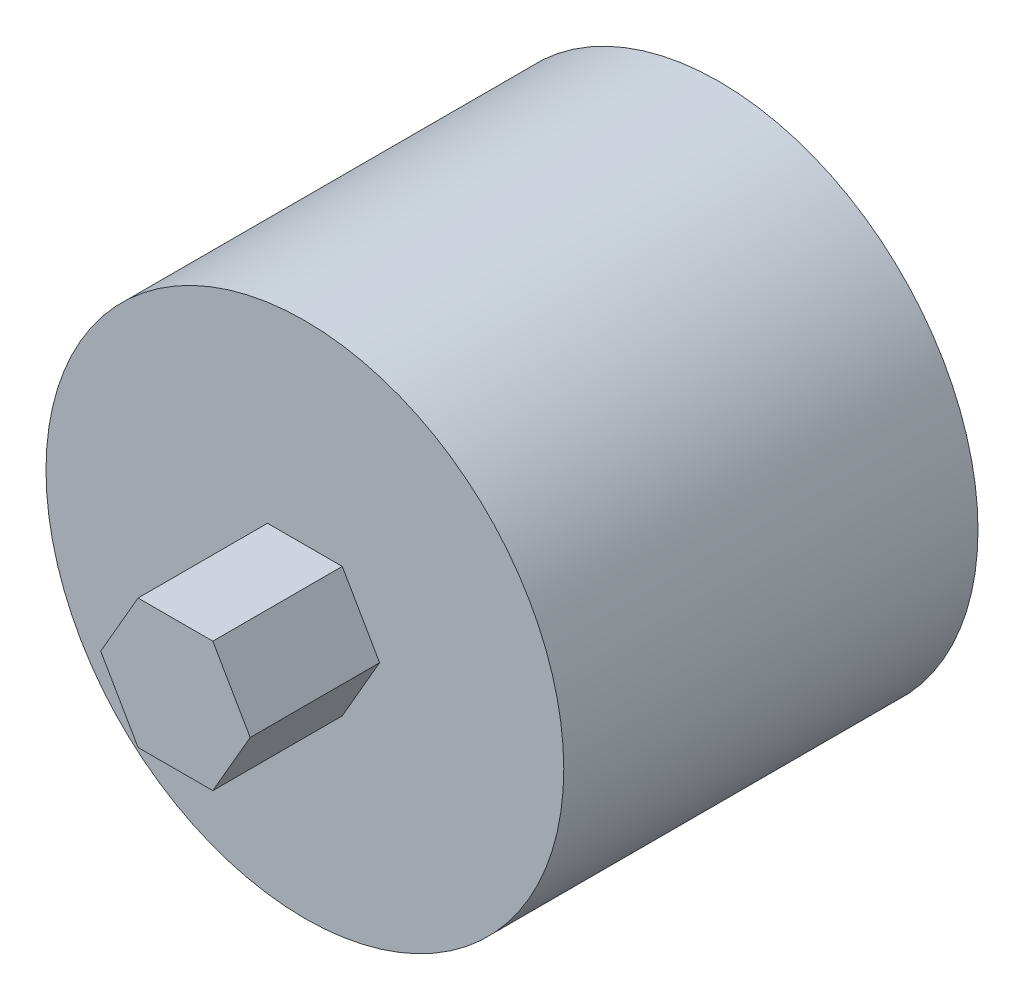
SolidWorks part; units mm, degrees
ref_plane "前视基准面" through (0, 0, 0) normal (0, 0, 1) x (1, 0, 0)
ref_plane "上视基准面" through (0, 0, 0) normal (0, 1, 0) x (1, 0, 0)
ref_plane "右视基准面" through (0, 0, 0) normal (1, 0, 0) x (0, 0, -1)
other "Configuration Table"
sketch "草图1" plane through (0, 0, 0) normal (0, 0, 1) x (1, 0, 0)
  line L0 (0, 0) -> (1.6914, 0.6156) construction
  line L1 (0, 0) -> (1.5832, 0.5954)
  line L2 (0, 0) -> (1.5832, -0.5954)
  line L3 (0, 0) -> (1.6914, -0.6156) construction
  line L4 (0, 0) -> (2.55, 0) construction
  line L5 (1.6914, 0.6156) -> (1.6914, -0.6156) construction
  circle A0 centre (0, 0) radius 1.65
  circle A1 centre (0, 0) radius 2.55
  circle A2 centre (0, 0) radius 1.6914 construction
  circle A3 centre (0, 0) radius 1.8 construction
  circle A4 centre (0, 0) radius 3
  spline S0 degree 4 poles (1.5832, 0.5954) (1.5953, 0.5999) (1.6299, 0.61) (1.6985, 0.6188) (1.8107, 0.6176) (1.9542, 0.5935) (2.1323, 0.5368) (2.3288, 0.4397) (2.527, 0.3033) (2.7182, 0.1281) (2.8863, -0.0692) (3.0309, -0.2841) (3.1583, -0.5243) (3.284, -0.8365) (3.3855, -1.2255) (3.4358, -1.6902) (3.4119, -2.2085) (3.3126, -2.7182) (3.1474, -3.2089) (2.918, -3.6756) (2.6387, -4.1089) (2.3029, -4.5102) (1.9385, -4.866) (1.5141, -5.1906) (1.1742, -5.4065) (0.7714, -5.6132) (0.5343, -5.7151) (0.2601, -5.8236) (0.1183, -5.8645) (-0.005, -5.9055) (-0.0434, -5.9147) (-0.0704, -5.9226) (-0.0848, -5.927) knots 0 0 0 0 0 0.005604 0.015718 0.02996 0.048734 0.068727 0.096889 0.125051 0.153212 0.181374 0.209535 0.237696 0.271429 0.327752 0.384075 0.440398 0.496721 0.553044 0.609367 0.66569 0.722013 0.778336 0.834659 0.890982 0.909091 0.954545 0.977273 0.988636 0.994318 1 1 1 1 1 construction
  spline S1 degree 4 poles (1.5832, 0.5954) (1.5953, 0.5999) (1.6299, 0.61) (1.6985, 0.6188) (1.8107, 0.6176) (1.9542, 0.5935) (2.1323, 0.5368) (2.3288, 0.4397) (2.527, 0.3033) (2.7182, 0.1281) (2.8863, -0.0692) (3.0309, -0.2841) (3.1583, -0.5243) (3.284, -0.8365) (3.3855, -1.2255) (3.4358, -1.6902) (3.4119, -2.2085) (3.3126, -2.7182) (3.1474, -3.2089) (2.918, -3.6756) (2.6387, -4.1089) (2.3029, -4.5102) (1.9385, -4.866) (1.5141, -5.1906) (1.1742, -5.4065) (0.8753, -5.5599) (0.734, -5.626) (0.6996, -5.6416) knots 0 0 0 0 0 0.005604 0.015718 0.02996 0.048734 0.068727 0.096889 0.125051 0.153212 0.181374 0.209535 0.237696 0.271429 0.327752 0.384075 0.440398 0.496721 0.553044 0.609367 0.66569 0.722013 0.778336 0.834659 0.890982 0.909091 0.909091 0.909091 0.909091 0.909091
  spline S2 degree 4 poles (1.5832, -0.5954) (1.5953, -0.5999) (1.6299, -0.61) (1.6985, -0.6188) (1.8107, -0.6176) (1.9542, -0.5935) (2.1323, -0.5368) (2.3288, -0.4397) (2.527, -0.3033) (2.7182, -0.1281) (2.8863, 0.0692) (3.0309, 0.2841) (3.1583, 0.5243) (3.284, 0.8365) (3.3855, 1.2255) (3.4358, 1.6902) (3.4119, 2.2085) (3.3126, 2.7182) (3.1474, 3.2089) (2.918, 3.6756) (2.6387, 4.1089) (2.3029, 4.5102) (1.9385, 4.866) (1.5141, 5.1906) (1.1742, 5.4065) (0.7714, 5.6132) (0.5343, 5.7151) (0.2601, 5.8236) (0.1183, 5.8645) (-0.005, 5.9055) (-0.0434, 5.9147) (-0.0704, 5.9226) (-0.0848, 5.927) knots 0 0 0 0 0 0.005604 0.015718 0.02996 0.048734 0.068727 0.096889 0.125051 0.153212 0.181374 0.209535 0.237696 0.271429 0.327752 0.384075 0.440398 0.496721 0.553044 0.609367 0.66569 0.722013 0.778336 0.834659 0.890982 0.909091 0.954545 0.977273 0.988636 0.994318 1 1 1 1 1 construction
  spline S3 degree 4 poles (1.5832, -0.5954) (1.5953, -0.5999) (1.6299, -0.61) (1.6985, -0.6188) (1.8107, -0.6176) (1.9542, -0.5935) (2.1323, -0.5368) (2.3288, -0.4397) (2.527, -0.3033) (2.7182, -0.1281) (2.8863, 0.0692) (3.0309, 0.2841) (3.1583, 0.5243) (3.284, 0.8365) (3.3855, 1.2255) (3.4358, 1.6902) (3.4119, 2.2085) (3.3126, 2.7182) (3.1474, 3.2089) (2.918, 3.6756) (2.6387, 4.1089) (2.3029, 4.5102) (1.9385, 4.866) (1.5141, 5.1906) (1.1742, 5.4065) (0.8753, 5.5599) (0.734, 5.626) (0.6996, 5.6416) knots 0 0 0 0 0 0.005604 0.015718 0.02996 0.048734 0.068727 0.096889 0.125051 0.153212 0.181374 0.209535 0.237696 0.271429 0.327752 0.384075 0.440398 0.496721 0.553044 0.609367 0.66569 0.722013 0.778336 0.834659 0.890982 0.909091 0.909091 0.909091 0.909091 0.909091
  point P16 (1.6914, 0)
  dimension "内啮合齿顶圆直径" = 3.3
  dimension "内啮合分度圆直径" = 3.6
  dimension "内啮合基圆直径" = 3.3829
  dimension "内啮合齿根圆直径" = 5.1
  dimension "外径" = 6
  dimension "渐开线镜像线夹角" = 20
extrude "凸台-拉伸1" add sketch "草图1" along normal blind 4 contours A4 | A0
extrude "切除-拉伸2" cut sketch "草图1<3>" along normal through all contours A0 S3 A1 S1 region at (2.0287, 0, 0)
sketch "草图1<3>" plane through (0, 0, 0) normal (0, 0, 1) x (1, 0, 0) same geometry as "草图1"
pattern_circular "阵列(圆周)1" count 9 over 360 about axis through (0, 0, 4) along (0, 0, 1) of "切除-拉伸2"
sketch "草图2" plane through (0, 0, 4) normal (0, 0, 1) x (1, 0, 0)
  line L1 (0.433, 0.75) -> (-0.433, 0.75)
  line L2 (-0.433, 0.75) -> (-0.866, 0)
  line L3 (-0.866, 0) -> (-0.433, -0.75)
  line L4 (-0.433, -0.75) -> (0.433, -0.75)
  line L5 (0.433, -0.75) -> (0.866, 0)
  line L6 (0.866, 0) -> (0.433, 0.75)
  circle A0 centre (0, 0) radius 3
  circle A1 centre (0, 0) radius 3 construction
  circle A2 centre (0, 0) radius 0.866
  circle A3 centre (0, 0) radius 1.1 construction
  dimension "D1" = 1.5
extrude "凸台-拉伸2" add sketch "草图2" along normal blind 0.8 contours A0
extrude "凸台-拉伸3" add sketch "草图2<3>" along normal blind 1.5 from surface contours L1 L2 L3 L4 L5 L6 starting at face at (3, 0, 4.8)
sketch "草图2<3>" plane through (0, 0, 4) normal (0, 0, 1) x (1, 0, 0) same geometry as "草图2"
equation "\"m\"= 0.4'模数"
equation "\"z1\"= 6'外啮合齿轮数"
equation "\"a\"= 20度'压力角"
equation "\"z2\"= 9'内啮合齿轮数"
equation "\"hax\"= 1'齿顶高系数"
equation "\"cx\"= 0.25'顶隙系数"
equation "\"ha\"= \"hax\" * \"m\"'齿顶高"
equation "\"hf\"= ( \"hax\" + \"cx\" ) * \"m\"'齿根高"
equation "\"d1\"= \"m\" * \"z1\"'外啮合分度圆直径"
equation "\"da1\"= ( \"z1\" + 2 ) * \"m\"'外啮合齿顶圆直径"
equation "\"df1\"= \"d1\" - 2 * \"hf\"'外啮合齿根圆直径"
equation "\"db1\"= \"d1\" * cos ( \"a\" )'外啮合基圆直径"
equation "\"p\"= \"m\" * PI'齿距"
equation "\"d2\"= \"m\" * \"z2\"'内啮合分度圆直径"
equation "\"db2\"= \"d2\" * cos ( \"a\" )'内啮合基圆直径"
equation "\"da2\"= ( \"z2\" - 2 ) * \"m\"'内啮合齿顶圆直径"
equation "\"df2\"= \"d2\" + 2 * \"hf\"'内啮合齿根圆直径"
equation "\"内啮合齿顶圆直径@草图1\" = \"da2\" + 1 * \"hf\""
equation "\"内啮合齿根圆直径@草图1\" = \"df2\" + 1 * \"hf\""
equation "\"内啮合分度圆直径@草图1\"= \"d2\""
equation "\"内啮合基圆直径@草图1\"= \"db2\""
equation "\"渐开线镜像线夹角@草图1\" = 360度 / 4 / \"z2\" + 360度 / 4 / \"z2\""
equation "\"do\"= IIF ( \"edo\" >= ( \"df2\" + 1 ) , \"edo\" , ( \"df2\" + 1 ) )'外圈直径"
equation "\"h\"= 4'厚度"
equation "\"外径@草图1\"= \"do\""
equation "\"厚度@凸台-拉伸1\"= \"h\""
equation "\"内啮合齿轮数@阵列(圆周)1\"= \"z2\""
equation "\"edo\"= 6'期望的外圈直径"
